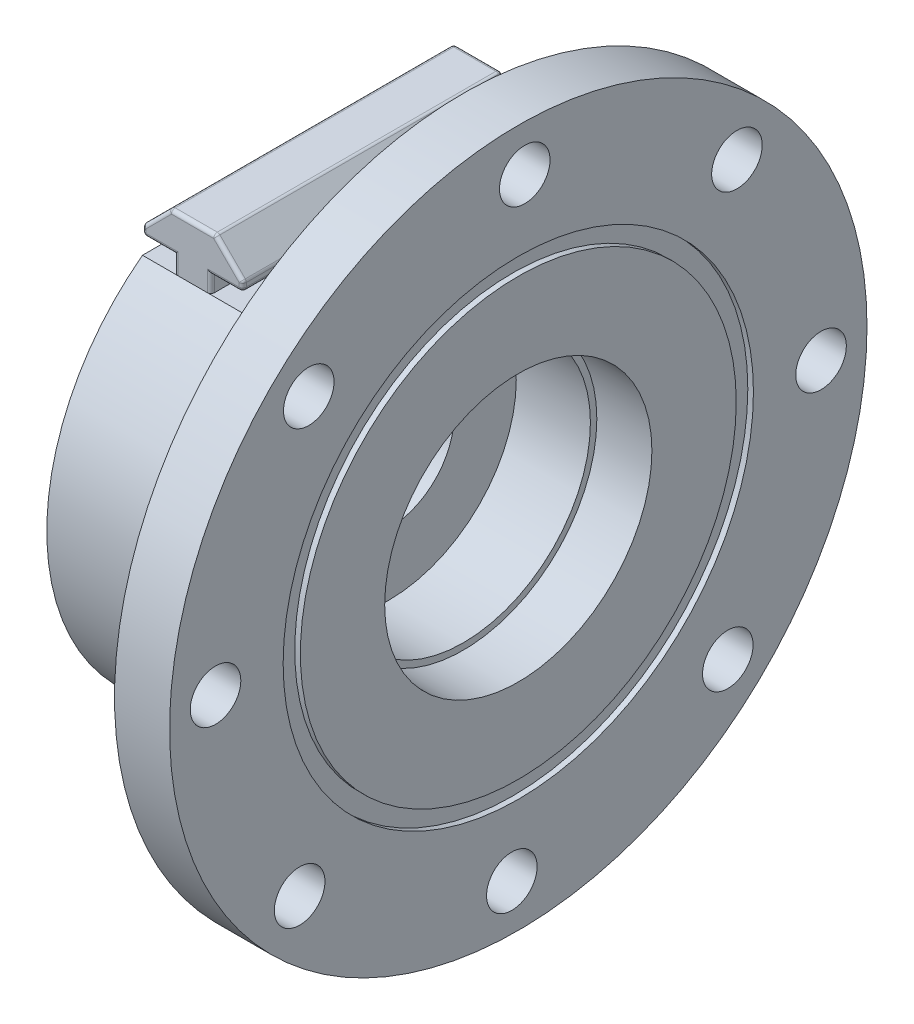
SolidWorks part; units mm, degrees
ref_plane "Front Plane" through (0, 0, 0) normal (0, 0, 1) x (1, 0, 0)
ref_plane "Top Plane" through (0, 0, 0) normal (0, 1, 0) x (1, 0, 0)
ref_plane "Right Plane" through (0, 0, 0) normal (1, 0, 0) x (0, 0, -1)
sketch "Main sketch" plane through (0, 0, 0) normal (0, 0, 1) x (1, 0, 0)
  line L0 (0, 9) -> (0, 19.995)
  line L1 (0, 19.995) -> (-8, 19.995)
  line L2 (-8, 19.995) -> (-8, 33.02)
  line L3 (-8, 33.02) -> (16.6116, 33.02)
  line L4 (16.6116, 33.02) -> (16.6116, 48.26)
  line L5 (16.6116, 48.26) -> (24.2316, 48.26)
  line L6 (24.2316, 48.26) -> (24.2316, 32.5438)
  line L7 (24.2316, 32.5438) -> (23.4537, 32.5438)
  line L8 (23.4537, 32.5438) -> (23.4537, 30.1625)
  line L9 (23.4537, 30.1625) -> (24.2316, 30.1625)
  line L10 (24.2316, 30.1625) -> (24.2316, 18.4912)
  line L11 (24.2316, 18.4912) -> (16.6116, 18.4912)
  line L12 (16.6116, 18.4912) -> (16.6116, 17.6022)
  line L13 (16.6116, 17.6022) -> (6.35, 17.6022)
  line L14 (6.35, 17.6022) -> (6.35, 9)
  line L15 (6.35, 9) -> (0, 9)
  line L16 (0, 0) -> (0, 9) construction
  dimension "D1" = 9
  dimension "D2" = 19.995
  dimension "D4" = 17.6022
  dimension "D5" = 8
  dimension "D6" = 48.26
  dimension "D7" = 18.4912
  dimension "D8" = 32.5437
  dimension "D11" = 6.35
  dimension "D12" = 10.2616
  dimension "D13" = 33.02
  dimension "D14" = 7.62
  dimension "D9" = 30.1625
  dimension "D10" = 0.7779
  dimension "D3" = 7.62
ref_axis "Axis1" through (71.9501, 0, 0) along (-1, 0, 0)
revolve "Revolve1" add sketch "Main sketch" angle 360 about axis through (71.9501, 0, 0) along (-1, 0, 0)
sketch "Sketch2" plane through (24.2316, 0, 0) normal (1, 0, 0) x (0, 0, -1)
  circle A0 centre (0, 0) radius 41.91 construction
  point P0 (0, 0)
  point P3 (-41.9005, 0.8944)
  point P4 (-30.2606, -28.9956)
  point P7 (-0.8944, -41.9005)
  point P8 (28.9956, -30.2606)
  point P9 (41.9005, -0.8944)
  point P10 (30.2606, 28.9956)
  point P11 (0.8944, 41.9005)
  point P12 (-28.9956, 30.2606)
  point P13 (0, 0)
  point P16 (0, 0)
  dimension "D2" = 83.82
  dimension "D1" = 8
hole_wizard "M6 Clearance Hole1" positions "Sketch2" profile "Sketch3" hole size "M6" standard "ISO" end condition through all
sketch "Sketch3" plane through (24.2316, 0, 0) normal (0, 1, 0) x (0, 0, -1)
  line L0 (0, 0) -> (0, 32.2316)
  line L1 (0, 32.2316) -> (3.5, 32.2316)
  line L2 (3.5, 32.2316) -> (3.5, 0)
  line L5 (3.5, 0) -> (0, 0)
  line L11 (0, -6.35) -> (0, 107.95) construction
  dimension "Thru Hole Dia." = 7
  dimension "Thru Hole Depth" = 32.2316
ref_plane "Plane1" through (0, 0, 33.02) normal (0, 0, 1) x (1, 0, 0)
ref_plane "Plane2" through (0, 33.02, 0) normal (0, 1, 0) x (1, 0, 0)
ref_plane "Plane3" through (0, 0, -33.02) normal (0, 0, -1) x (-1, 0, 0)
sketch "Sketch4" plane through (0, 33.02, 0) normal (0, 1, 0) x (1, 0, 0)
  line L0 (-8, -33.02) -> (16.6116, -33.02) construction
  line L1 (16.6116, 33.02) -> (16.6116, -33.02) construction
  line L2 (16.6116, 33.02) -> (-8, 33.02) construction
  line L3 (-8, 33.02) -> (-8, -33.02) construction
  line L4 (-8, -33.02) -> (16.6116, -33.02)
  line L5 (16.6116, 33.02) -> (16.6116, -33.02)
  line L6 (16.6116, 33.02) -> (-8, 33.02)
  line L7 (-8, 33.02) -> (-8, -33.02)
extrude "Cut-Extrude1" cut sketch "Sketch4" against normal blind 6.5786
ref_plane "Plane4" through (0, 0, -19.7781) normal (0, 0, 1) x (1, 0, 0)
ref_plane "Plane5" through (0, 0, 19.7781) normal (0, 0, -1) x (-1, 0, 0)
sketch "Sketch5" plane through (0, 0, 19.7781) normal (0, 0, -1) x (-1, 0, 0)
  line L0 (8, 26.4414) -> (-16.6116, 26.4414) construction
  line L1 (8, 26.4414) -> (-16.6116, 26.4414)
  line L2 (-1.4742, 26.4414) -> (-1.4742, 28.8036)
  line L3 (-1.4742, 28.8036) -> (-5.8684, 28.8036)
  line L4 (-5.8684, 28.8036) -> (-5.8684, 30.0736)
  line L5 (-5.8684, 30.0736) -> (-2.0584, 33.8836)
  line L6 (-2.0584, 33.8836) -> (4.19, 33.8836)
  line L7 (1.0658, 33.8836) -> (1.0658, 26.4414) construction
  line L8 (3.6058, 26.4414) -> (-1.4742, 26.4414)
  line L9 (3.6058, 26.4414) -> (3.6058, 28.8036)
  line L10 (3.6058, 28.8036) -> (8, 28.8036)
  line L11 (8, 28.8036) -> (8, 30.0736)
  line L12 (8, 30.0736) -> (4.19, 33.8836)
  line L13 (8, -33.02) -> (8, 26.4414) construction
  dimension "D1" = 2.54
  dimension "D2" = 2.3622
  dimension "D3" = 135
  dimension "D4" = 5.08
  dimension "D5" = 6.9342
  dimension "D6" = 1.27
extrude "Boss-Extrude1" add sketch "Sketch5" along normal up to surface (39.5562 mm away) contours L7 L6 L5 L4 L3 L2 L8 | L6 L7 L1 L9 L10 L11 L12 region at (-3.6753, 30.4149, 19.7781) region at (1.5437, 30.4149, 19.7781) up to plane "Plane4"
fillet "Fillet1" radius 0.508 24 edges at (-1.0658, 33.8836, -19.7781) (1.4742, 27.6225, 19.7781) (5.8684, 29.4386, 19.7781) (3.6713, 28.8036, 19.7781) (3.9634, 31.9786, 19.7781) (-1.0658, 33.8836, 19.7781) (-5.8029, 28.8036, 19.7781) (-3.6058, 27.6225, 19.7781) (1.4742, 27.6225, -19.7781) (-3.6058, 27.6225, -19.7781) (-5.8029, 28.8036, -19.7781) (-6.095, 31.9786, -19.7781) (-4.19, 33.8836, 0) (-6.095, 31.9786, 19.7781) (-8, 29.4386, 19.7781) (-8, 30.0736, 0) (-8, 28.8036, 0) (-8, 29.4386, -19.7781) (3.9634, 31.9786, -19.7781) (5.8684, 29.4386, -19.7781) (3.6713, 28.8036, -19.7781) (2.0584, 33.8836, 0) (5.8684, 30.0736, 0) (5.8684, 28.8036, 0)
mirror "Mirror1" about plane through (0, 0, 0) normal (0, 1, 0) of "Fillet1", "Boss-Extrude1", "Cut-Extrude1"
equation "\"Shaft_OD\"= 17mm'outer diameter of shaft"
equation "\"O_Ring_ID\"= 2.375in"
equation "\"O_Ring_CS\"= 1 / 16in'cross section"
equation "\"Bearing_OD\"= 39.99mm"
equation "\"Bearing_Depth\"= 8mm'depth bearing goes into the casing"
equation "\"Stationary_Face_Seal_OD\"= 1.386in"
equation "\"Flange_Dia\"= 3.8in"
equation "\"Screw_Dia\"= 6mm"
equation "\"Seal_Space\" = .3in"
equation "\"D1@Main sketch\"=\"Shaft_OD\" / 2 + .5mm"
equation "\"D2@Main sketch\" = \"Bearing_OD\" / 2"
equation "\"D4@Main sketch\" = \"Stationary_Face_Seal_OD\" / 2"
equation "\"D5@Main sketch\" = \"Bearing_Depth\""
equation "\"D6@Main sketch\" = \"Flange_Dia\" / 2"
equation "\"Seal_Area_Dia\"= 37mm"
equation "\"D7@Main sketch\"=\"Seal_space_Dia\"/2"
equation "\"D8@Main sketch\"=\"O_Ring_ID\" / 2 + \"O_Ring_CS\" * 1.5"
equation "\"Face_Seal_Height\" = 0.404in"
equation "\"D12@Main sketch\" = \"Face_Seal_Height\""
equation "\"Housing_OR\"= 1.3in'Outer radius of housing"
equation "\"D13@Main sketch\"=\"Housing_OR\""
equation "\"D10@Main sketch\"=\"O_Ring_CS\"*.49"
equation "\"D9@Main sketch\"=\"O_Ring_ID\"/2"
equation "\"D2@Sketch2\"=\"Flange_Dia\"-\"Screw_offset\""
equation "\"Screw_offset\"= .5in'offset of screws from flange OD."
equation "\"Seal_space_Dia\"= \"Stationary_Face_Seal_OD\" + .07'diameter of the space for the face seal"
